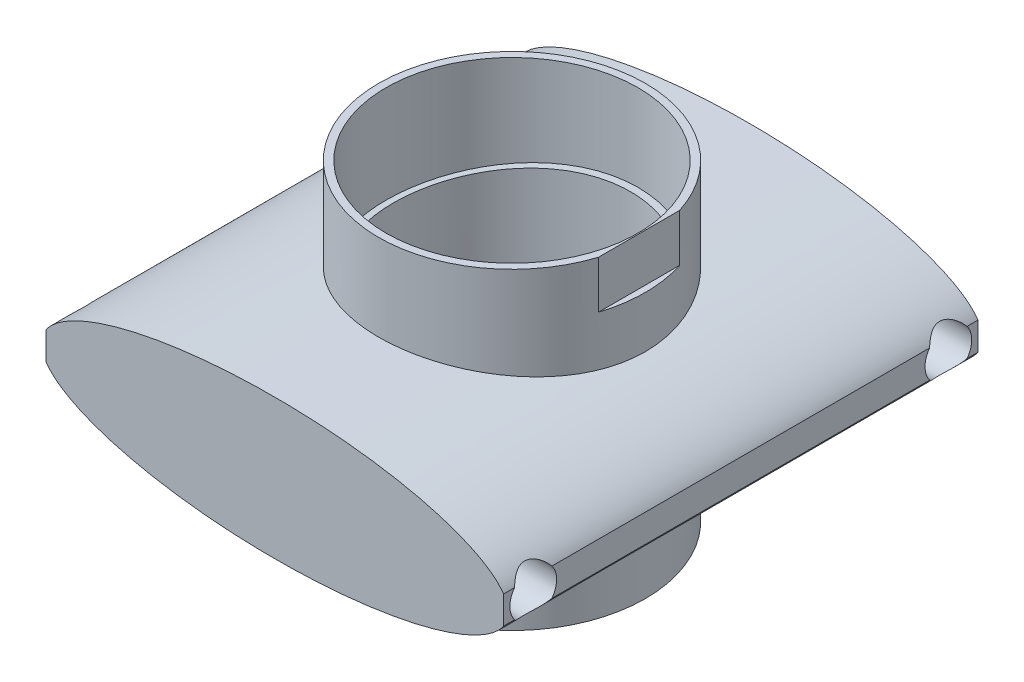
SolidWorks part; units mm, degrees
ref_plane "Front Plane" through (0, 0, 0) normal (0, 0, 1) x (1, 0, 0)
ref_plane "Top Plane" through (0, 0, 0) normal (0, 1, 0) x (1, 0, 0)
ref_plane "Right Plane" through (0, 0, 0) normal (1, 0, 0) x (0, 0, -1)
sketch "Sketch1" plane through (0, 0, 0) normal (0, 1, 0) x (1, 0, 0)
  circle A0 centre (0, 0) radius 26.9875
  circle A1 centre (0, 0) radius 28.575
  dimension "D1" = 53.975
  dimension "D2" = 57.15
extrude "Boss-Extrude1" add sketch "Sketch1" along normal blind 67
sketch "Sketch2" plane through (0, 0, 0) normal (0, 0, 1) x (1, 0, 0)
  line L0 (-50, 33.5) -> (50, 33.5)
  line L1 (0, 48.5) -> (0, 18.5)
  ellipse E0 centre (0, 33.5) end of major axis (50, 33.5) minor radius 15
  dimension "D1" = 30
  dimension "D2" = 100
extrude "Boss-Extrude2" add sketch "Sketch2" along normal blind 50.8 and the other way blind 50.8 contours L1 E0 L0 | L0 E0 L1 | L1 E0 L0 | L0 E0 L1 region at (-21.2207, 39.8662, 0) region at (-21.2207, 27.1338, 0) region at (21.2207, 39.8662, 0) region at (21.2207, 27.1338, 0)
sketch "Sketch4" plane through (0, 67, 0) normal (0, 1, 0) x (1, 0, 0)
  circle A0 centre (0, 0) radius 25.4
extrude "Cut-Extrude1" cut sketch "Sketch4" against normal blind 76.2
sketch "Sketch7" plane through (0, 67, 0) normal (0, 1, 0) x (1, 0, 0)
  line L1 (29.9358, -17.9247) -> (27.2202, -17.9247)
  line L2 (29.9358, -17.9247) -> (29.9358, 20.5522)
  line L3 (29.9358, 20.5522) -> (27.2202, 20.5522)
  line L4 (27.2202, -17.9247) -> (27.2202, 20.5522)
extrude "Cut-Extrude2" cut sketch "Sketch7" against normal blind 10.2
sketch "Sketch10" plane through (0, 0, 50.8) normal (0, 0, 1) x (1, 0, 0)
  line L0 (0, 48.5) -> (0, 18.5)
  line L1 (20.801, 47.1403) -> (20.801, 19.8597)
  arc A0 (20.801, 19.8597) -> (20.801, 47.1403) centre (0, 33.5) ccw
  ellipse E1 centre (0, 33.5) end of major axis (50, 33.5) minor radius 15
  ellipse E2 centre (0, 33.5) end of major axis (50, 33.5) minor radius 15
  dimension "D1" = 0
revolve "Revolve2" [suppressed] add sketch "Sketch10" angle 360 about L0
mirror "Mirror2" [suppressed] about plane through (0, 0, 0) normal (0, 0, 1)
sketch "Sketch11" [suppressed] plane through (0, 67, 0) normal (0, 1, 0) x (1, 0, 0)
  line L1 (0, 76.2) -> (50, 76.2) construction
  circle A0 centre (0, -76.2) radius 5
  circle A1 centre (0, 76.2) radius 5
  dimension "D1" = 10
  dimension "D2" = 10
  dimension "D3" = 76.2
  dimension "D4" = 76.2
extrude "Cut-Extrude4" [suppressed] cut sketch "Sketch11" against normal blind 80
sketch "Sketch12" plane through (0, 0, 0) normal (1, 0, 0) x (0, 0, -1)
  line L0 (8.6942, 67) -> (-8.6942, 67) construction
  circle A0 centre (-44.45, 33.5) radius 5
  point P4 (0, 67)
  dimension "D1" = 10
  dimension "D2" = 44.45
extrude "Cut-Extrude5" cut sketch "Sketch12" against normal blind 64 and the other way blind 65
mirror "Mirror3" about plane through (0, 0, 0) normal (0, 0, 1) of "Cut-Extrude5"
sketch "Sketch13" plane through (0, 0, 50.8) normal (0, 0, 1) x (1, 0, 0)
  line L0 (0, 48.5) -> (0, 18.5)
  line L1 (55.0909, 43.7391) -> (49, 43.7391)
  line L2 (55.0909, 43.7391) -> (55.0909, 24.101)
  line L3 (55.0909, 24.101) -> (49, 24.101)
  line L4 (49, 43.7391) -> (49, 24.101)
  line L5 (-49, 43.7391) -> (-49, 24.101)
  line L6 (-55.0909, 24.101) -> (-49, 24.101)
  line L7 (-55.0909, 43.7391) -> (-55.0909, 24.101)
  line L8 (-55.0909, 43.7391) -> (-49, 43.7391)
  ellipse E0 centre (0, 33.5) end of major axis (50, 33.5) minor radius 15 construction
  ellipse M3 centre (0, 33.5) end of major axis (50, 33.5) minor radius 15
  dimension "D1" = 49
extrude "Cut-Extrude6" cut sketch "Sketch13" against normal blind 110 contours L5 M3 | L8 L7 L6 L5 M3 | L4 M3 | L4 L3 L2 L1 region at (49.4003, 33.5, 50.8) region at (-52.1367, 33.9346, 50.8) region at (-49.4003, 33.5, 50.8)
equation "\"d1\"= 1.5cm'membrane smaller diameter"
equation "\"r0\"= 1.5in'membrane circular radius"
equation "\"d2\"= sqr ( 2 * \"r0\" ^ 2 - \"d1\" ^ 2 )'membrane larger radius"
